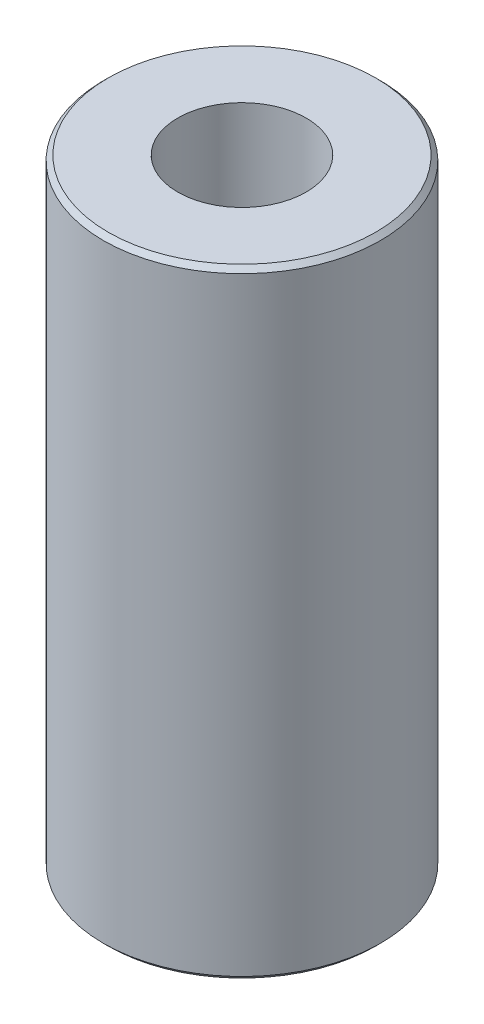
SolidWorks part; units mm, degrees
ref_plane "Front Plane" through (0, 0, 0) normal (0, 0, 1) x (1, 0, 0)
ref_plane "Top Plane" through (0, 0, 0) normal (0, 1, 0) x (1, 0, 0)
ref_plane "Right Plane" through (0, 0, 0) normal (1, 0, 0) x (0, 0, -1)
sketch "Sketch1" plane through (0, 0, 0) normal (0, 1, 0) x (1, 0, 0)
  circle A0 centre (0, 0) radius 60
  dimension "SHAFT_OD" = 120
extrude "Boss-Extrude1" add sketch "Sketch1" along normal blind 267.7894
sketch "Sketch2" plane through (0, 0, 0) normal (0, 1, 0) x (1, 0, 0)
  circle A0 centre (0, 0) radius 27.8214
  dimension "BORE_D" = 55.6428
extrude "Cut-Extrude1" cut sketch "Sketch2" along normal through all
chamfer "Chamfer1" distance 2.0814 angle 45 2 edges at (0, 267.7894, 60) (0, 0, 60)
